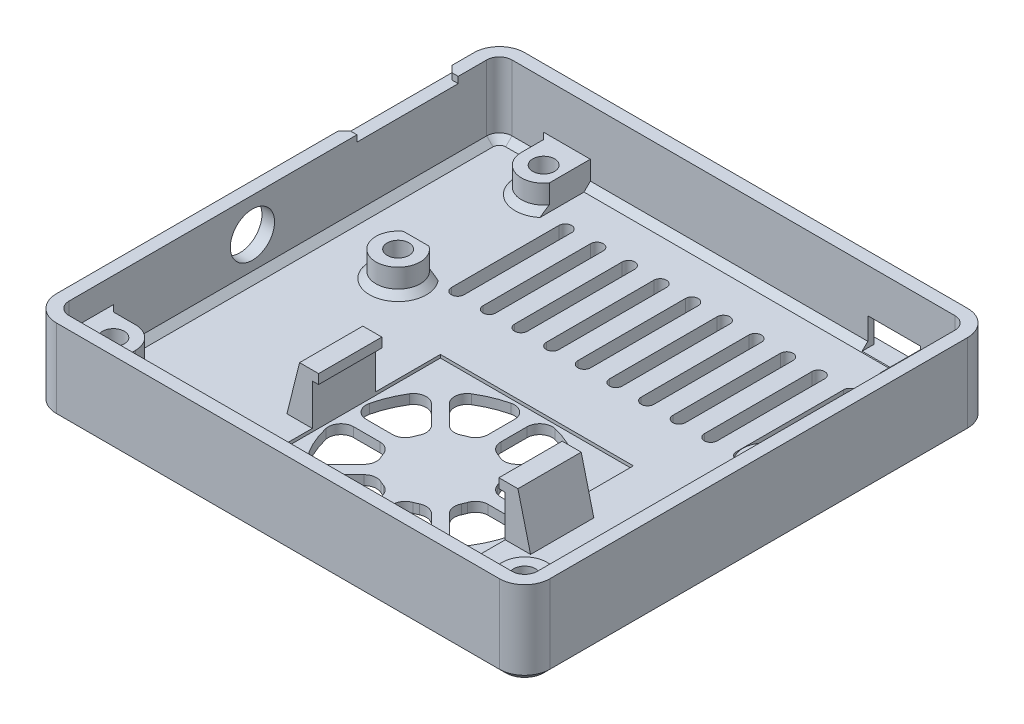
SolidWorks part; units mm, degrees
ref_plane "Front Plane" through (0, 0, 0) normal (0, 0, 1) x (1, 0, 0)
ref_plane "Top Plane" through (0, 0, 0) normal (0, 1, 0) x (1, 0, 0)
ref_plane "Right Plane" through (0, 0, 0) normal (1, 0, 0) x (0, 0, -1)
sketch "Sketch1" plane through (0, 0, 0) normal (0, 1, 0) x (1, 0, 0)
  line L0 (-65.617, -16.3721) -> (-0.617, -16.3721)
  line L1 (-62.117, 10.1279) -> (-4.117, 10.1279)
  line L2 (-62.117, 10.1279) -> (-62.117, -12.8721)
  line L3 (-65.617, 13.6279) -> (-0.617, 13.6279)
  line L4 (-65.617, 13.6279) -> (-65.617, -16.3721)
  line L5 (-62.117, -12.8721) -> (-4.117, -12.8721)
  line L6 (-0.617, 13.6279) -> (-0.617, -16.3721)
  line L7 (-4.117, 10.1279) -> (-4.117, -12.8721)
  line L8 (-24.217, 16.7282) -> (-24.217, 15.4455)
  line L9 (-11.617, 16.7282) -> (-11.617, 15.4455)
  dimension "D1" = 65
  dimension "D2" = 30
  dimension "D3" = 58
  dimension "D4" = 23
  dimension "D5" = 3.5
  dimension "D6" = 3.5
sketch "Sketch2" plane through (0, 0, 0) normal (0, 1, 0) x (1, 0, 0)
  line L6 (-73.617, 13.6279) -> (-73.617, -16.3721)
  line L7 (-73.617, 12.6279) -> (-73.617, -53.3721)
  line L10 (-71.617, -55.3721) -> (-1.617, -55.3721)
  line L11 (-75.617, 12.6279) -> (-75.617, -53.3721)
  line L12 (0.383, 14.6279) -> (0.383, -16.3721)
  line L13 (-65.617, 14.6279) -> (0.383, 14.6279)
  line L14 (0.383, 12.6279) -> (0.383, -53.3721)
  line L15 (-71.617, 14.6279) -> (-1.617, 14.6279)
  line L16 (-71.617, -57.3721) -> (-1.617, -57.3721)
  line L17 (2.383, 12.6279) -> (2.383, -53.3721)
  line L18 (-71.617, 16.6279) -> (-1.617, 16.6279)
  arc A0 (-71.617, -55.3721) -> (-73.617, -53.3721) centre (-71.617, -53.3721) cw
  arc A1 (-1.617, -55.3721) -> (0.383, -53.3721) centre (-1.617, -53.3721) ccw
  arc A2 (0.383, 12.6279) -> (-1.617, 14.6279) centre (-1.617, 12.6279) ccw
  arc A3 (-71.617, 14.6279) -> (-73.617, 12.6279) centre (-71.617, 12.6279) ccw
  arc A4 (-71.617, -57.3721) -> (-75.617, -53.3721) centre (-71.617, -53.3721) cw
  arc A5 (-1.617, -57.3721) -> (2.383, -53.3721) centre (-1.617, -53.3721) ccw
  arc A6 (2.383, 12.6279) -> (-1.617, 16.6279) centre (-1.617, 12.6279) ccw
  arc A7 (-71.617, 16.6279) -> (-75.617, 12.6279) centre (-71.617, 12.6279) ccw
  dimension "D4" = 2
  dimension "D3" = 70
  dimension "D1" = 8
  dimension "D2" = 1
  dimension "D5" = 2
extrude "Boss-Extrude1" add sketch "Sketch2" along normal blind 13.4
extrude "Boss-Extrude2" add sketch "Sketch2<3>" along normal blind 2 contours L15 A3 L7 A0 L10 A1 L14 A2 region at (-36.617, 0, 20.3721)
sketch "Sketch2<3>" plane through (0, 0, 0) normal (0, 1, 0) x (1, 0, 0) same geometry as "Sketch2"
sketch "Sketch4" plane through (0, 2, 0) normal (0, 1, 0) x (1, 0, 0)
  line L0 (-59.2343, 14.6279) -> (-59.2343, 8.1428)
  line L1 (-1.617, 14.6279) -> (-71.617, 14.6279) construction
  line L2 (-4.117, 6.6279) -> (0.383, 6.6279)
  line L3 (0.383, -53.3721) -> (0.383, 12.6279) construction
  line L4 (0.383, 6.6279) -> (0.383, 12.6279)
  line L5 (-7.0825, 14.6279) -> (-1.617, 14.6279)
  line L6 (-4.117, -9.3721) -> (0.383, -9.3721)
  line L7 (0.383, -9.3721) -> (0.383, -16.3721)
  line L8 (0.383, -16.3721) -> (-4.117, -16.3721)
  line L9 (-64.1397, -10.0158) -> (-60.0943, -10.0158)
  line L10 (-59.2343, 14.6279) -> (-65.617, 14.6279)
  line L11 (-65.617, 14.6279) -> (-65.617, 10.1279)
  line L12 (-7.0825, 14.6279) -> (-7.0825, 8.269)
  arc A0 (-7.0825, 8.269) -> (-4.117, 6.6279) centre (-4.117, 10.1279) ccw
  arc A1 (-4.117, -9.3721) -> (-4.117, -16.3721) centre (-4.117, -12.8721) ccw
  arc A2 (-64.1397, -10.0158) -> (-60.0943, -10.0158) centre (-62.117, -12.8721) ccw
  arc A3 (-65.617, 10.1279) -> (-59.2343, 8.1428) centre (-62.117, 10.1279) ccw
  arc A4 (0.383, 12.6279) -> (-1.617, 14.6279) centre (-1.617, 12.6279) ccw
  dimension "D1" = 2
extrude "Boss-Extrude3" add sketch "Sketch4" along normal offset from surface (4 mm away) 7.4 up to face at (-36.617, 13.4, 20.3721)
hole_wizard "CSK for #4 Flat Head Socket Cap Screw1" positions "Sketch6" profile "Sketch5" countersink size "#4" standard "ANSI Inch" end condition through all
sketch "Sketch6" plane through (0, 0, 0) normal (0, -1, 0) x (-1, 0, 0)
  point P0 (4.117, 10.1279)
  point P4 (62.117, 10.1279)
  point P8 (4.117, -12.8721)
  point P12 (62.117, -12.8721)
sketch "Sketch5" plane through (-4.117, 0, -10.1279) normal (1, 0, 0) x (0, 0, -1)
  line L0 (0, 0) -> (0, 13.4)
  line L1 (0, 13.4) -> (1.7272, 13.4)
  line L2 (1.7272, 13.4) -> (1.7272, 1.8805)
  line L3 (1.7272, 1.8805) -> (3.3619, 0)
  line L5 (3.3619, 0) -> (0, 0)
  line L6 (-1.7272, 1.8805) -> (-3.3619, 0) construction
  line L11 (0, -6.35) -> (0, 107.95) construction
  dimension "Thru Hole Dia." = 3.4544
  dimension "Thru Hole Depth" = 13.4
  dimension "Near C'Sink Dia." = 6.7237
  dimension "Near C'Sink Angle" = 82
sketch "Sketch7" plane through (0, 0, -16.6279) normal (0, 0, -1) x (-1, 0, 0)
  line L0 (11.2325, 6.5) -> (11.2325, 2.1) construction
  line L1 (7.0825, 6.5) -> (15.3825, 6.5)
  line L2 (7.0825, 6.5) -> (7.0825, 2.1)
  line L3 (7.0825, 2.1) -> (15.3825, 2.1)
  line L4 (15.3825, 6.5) -> (15.3825, 2.1)
  line L5 (1.617, 6) -> (7.0825, 6) construction
  line L7 (7.0825, 6) -> (7.0825, 2) construction
  dimension "D1" = 8.3
  dimension "D2" = 0.5
  dimension "D3" = 0
  dimension "D4" = 4.4
extrude "Cut-Extrude1" cut sketch "Sketch7" against normal up to next
sketch "Sketch9" plane through (0, 2, 0) normal (0, 1, 0) x (1, 0, 0)
  line L0 (0.383, -16.3721) -> (0.383, -53.3721) construction
  line L1 (-71.617, -55.3721) -> (-1.617, -55.3721) construction
  line L2 (-73.617, 12.6279) -> (-73.617, -53.3721) construction
  line L3 (-69.117, -47.3721) -> (-73.617, -47.3721)
  line L4 (-65.617, -50.8721) -> (-65.617, -55.3721)
  line L5 (-71.617, -55.3721) -> (-1.617, -55.3721) construction
  line L6 (-73.617, -47.3721) -> (-73.617, -53.3721)
  line L7 (-65.617, -55.3721) -> (-71.617, -55.3721)
  line L8 (-4.117, -47.3721) -> (0.383, -47.3721)
  line L9 (0.383, -47.3721) -> (0.383, -53.3721)
  line L10 (-7.617, -50.8721) -> (-7.617, -55.3721)
  line L11 (-7.617, -55.3721) -> (-1.617, -55.3721)
  arc A0 (-4.117, -47.3721) -> (-7.617, -50.8721) centre (-4.117, -50.8721) ccw
  arc A1 (-65.617, -50.8721) -> (-69.117, -47.3721) centre (-69.117, -50.8721) ccw
  arc A2 (-73.617, -53.3721) -> (-71.617, -55.3721) centre (-71.617, -53.3721) ccw
  arc A3 (-1.617, -55.3721) -> (0.383, -53.3721) centre (-1.617, -53.3721) ccw
  dimension "D1" = 4.5
  dimension "D2" = 4.5
  dimension "D3" = 4.5
  dimension "D4" = 4.5
  dimension "D5" = 2
  dimension "D6" = 2
extrude "Boss-Extrude4" add sketch "Sketch9" along normal offset from surface (7.4 mm away) 4 up to face at (-36.617, 13.4, 20.3721)
hole_wizard "CSK for #4 Flat Head Socket Cap Screw2" positions "Sketch11" profile "Sketch10" countersink size "#4" standard "ANSI Inch" end condition through all
sketch "Sketch11" plane through (0, 0, 0) normal (0, -1, 0) x (-1, 0, 0)
  point P0 (4.117, -50.8721)
  point P4 (69.117, -50.8721)
sketch "Sketch10" plane through (-4.117, 0, 50.8721) normal (1, 0, 0) x (0, 0, -1)
  line L0 (0, 0) -> (0, 13.4)
  line L1 (0, 13.4) -> (1.7272, 13.4)
  line L2 (1.7272, 13.4) -> (1.7272, 1.8805)
  line L3 (1.7272, 1.8805) -> (3.3619, 0)
  line L5 (3.3619, 0) -> (0, 0)
  line L6 (-1.7272, 1.8805) -> (-3.3619, 0) construction
  line L11 (0, -6.35) -> (0, 107.95) construction
  dimension "Thru Hole Dia." = 3.4544
  dimension "Thru Hole Depth" = 13.4
  dimension "Near C'Sink Dia." = 6.7237
  dimension "Near C'Sink Angle" = 82
chamfer "Chamfer1" distance 1 angle 45 8 edges at (-65.617, 4, -14.6279) (-65.617, 5.7, 55.3721) (-73.617, 5.7, 47.3721) (0.383, 4, 9.3721) (0.383, 4, -6.6279) (0.383, 4, 16.3721) (0.383, 5.7, 47.3721) (-7.617, 5.7, 55.3721)
chamfer "Chamfer2" distance 1 angle 45 21 edges at (-62.117, 2, 16.3721) (-65.617, 2, -11.8779) (-63.1564, 2, -6.7858) (-2.367, 2, -6.6279) (-5.8117, 2, -7.0655) (0.383, 2, 1.3721) (-2.367, 2, 9.3721) (-2.367, 2, 16.3721) (0.383, 2, 31.8721) (-2.367, 2, 47.3721) (-7.617, 2, 52.6221) (-6.5919, 2, 48.3973) (-36.617, 2, 55.3721) (-65.617, 2, 52.6221) (-70.867, 2, 47.3721) (-66.6421, 2, 48.3973) (-69.117, 2, -14.6279) (-73.0312, 2, -14.0421) (-73.617, 2, 16.8721) (-7.617, 2, 12.8721) (-33.1584, 2, -14.6279)
chamfer "Chamfer3" distance 1 angle 45 8 edges at (2.383, 0, 20.3721) (1.2114, 0, -15.4563) (1.2114, 0, 56.2006) (-36.617, 0, -16.6279) (-36.617, 0, 57.3721) (-74.4454, 0, -15.4563) (-74.4454, 0, 56.2006) (-75.617, 0, 20.3721)
chamfer "Chamfer4" distance 1 angle 45 2 edges at (-15.3825, 4.3, -16.6279) (-7.0825, 4.3, -16.6279)
sketch "Sketch12" plane through (0, 0, 0) normal (0, -1, 0) x (1, 0, 0)
  line L0 (-55.6605, 9.9113) -> (-55.6605, -7.0887) construction
  line L1 (-54.6605, 9.9113) -> (-54.6605, -7.0887)
  line L2 (-56.6605, 9.9113) -> (-56.6605, -7.0887)
  line L3 (-50.6605, 9.9113) -> (-50.6605, -7.0887) construction
  line L4 (-49.6605, 9.9113) -> (-49.6605, -7.0887)
  line L5 (-51.6605, 9.9113) -> (-51.6605, -7.0887)
  line L6 (-45.6605, 9.9113) -> (-45.6605, -7.0887) construction
  line L7 (-44.6605, 9.9113) -> (-44.6605, -7.0887)
  line L8 (-46.6605, 9.9113) -> (-46.6605, -7.0887)
  line L9 (-40.6605, 9.9113) -> (-40.6605, -7.0887) construction
  line L10 (-39.6605, 9.9113) -> (-39.6605, -7.0887)
  line L11 (-41.6605, 9.9113) -> (-41.6605, -7.0887)
  line L12 (-35.6605, 9.9113) -> (-35.6605, -7.0887) construction
  line L13 (-34.6605, 9.9113) -> (-34.6605, -7.0887)
  line L14 (-36.6605, 9.9113) -> (-36.6605, -7.0887)
  line L15 (-30.6605, 9.9113) -> (-30.6605, -7.0887) construction
  line L16 (-29.6605, 9.9113) -> (-29.6605, -7.0887)
  line L17 (-31.6605, 9.9113) -> (-31.6605, -7.0887)
  line L18 (-25.6605, 9.9113) -> (-25.6605, -7.0887) construction
  line L19 (-24.6605, 9.9113) -> (-24.6605, -7.0887)
  line L20 (-26.6605, 9.9113) -> (-26.6605, -7.0887)
  line L21 (-20.6605, 9.9113) -> (-20.6605, -7.0887) construction
  line L22 (-19.6605, 9.9113) -> (-19.6605, -7.0887)
  line L23 (-21.6605, 9.9113) -> (-21.6605, -7.0887)
  line L24 (-15.6605, 9.9113) -> (-15.6605, -7.0887) construction
  line L25 (-14.6605, 9.9113) -> (-14.6605, -7.0887)
  line L26 (-16.6605, 9.9113) -> (-16.6605, -7.0887)
  line L27 (-10.6605, 9.9113) -> (-10.6605, -7.0887) construction
  line L28 (-9.6605, 9.9113) -> (-9.6605, -7.0887)
  line L29 (-11.6605, 9.9113) -> (-11.6605, -7.0887)
  arc A0 (-54.6605, 9.9113) -> (-56.6605, 9.9113) centre (-55.6605, 9.9113) ccw
  arc A1 (-56.6605, -7.0887) -> (-54.6605, -7.0887) centre (-55.6605, -7.0887) ccw
  arc A2 (-49.6605, 9.9113) -> (-51.6605, 9.9113) centre (-50.6605, 9.9113) ccw
  arc A3 (-51.6605, -7.0887) -> (-49.6605, -7.0887) centre (-50.6605, -7.0887) ccw
  arc A4 (-44.6605, 9.9113) -> (-46.6605, 9.9113) centre (-45.6605, 9.9113) ccw
  arc A5 (-46.6605, -7.0887) -> (-44.6605, -7.0887) centre (-45.6605, -7.0887) ccw
  arc A6 (-39.6605, 9.9113) -> (-41.6605, 9.9113) centre (-40.6605, 9.9113) ccw
  arc A7 (-41.6605, -7.0887) -> (-39.6605, -7.0887) centre (-40.6605, -7.0887) ccw
  arc A8 (-34.6605, 9.9113) -> (-36.6605, 9.9113) centre (-35.6605, 9.9113) ccw
  arc A9 (-36.6605, -7.0887) -> (-34.6605, -7.0887) centre (-35.6605, -7.0887) ccw
  arc A10 (-29.6605, 9.9113) -> (-31.6605, 9.9113) centre (-30.6605, 9.9113) ccw
  arc A11 (-31.6605, -7.0887) -> (-29.6605, -7.0887) centre (-30.6605, -7.0887) ccw
  arc A12 (-24.6605, 9.9113) -> (-26.6605, 9.9113) centre (-25.6605, 9.9113) ccw
  arc A13 (-26.6605, -7.0887) -> (-24.6605, -7.0887) centre (-25.6605, -7.0887) ccw
  arc A14 (-19.6605, 9.9113) -> (-21.6605, 9.9113) centre (-20.6605, 9.9113) ccw
  arc A15 (-21.6605, -7.0887) -> (-19.6605, -7.0887) centre (-20.6605, -7.0887) ccw
  arc A16 (-14.6605, 9.9113) -> (-16.6605, 9.9113) centre (-15.6605, 9.9113) ccw
  arc A17 (-16.6605, -7.0887) -> (-14.6605, -7.0887) centre (-15.6605, -7.0887) ccw
  arc A18 (-9.6605, 9.9113) -> (-11.6605, 9.9113) centre (-10.6605, 9.9113) ccw
  arc A19 (-11.6605, -7.0887) -> (-9.6605, -7.0887) centre (-10.6605, -7.0887) ccw
  point P2 (-55.6605, 1.4113)
  point P10 (-50.6605, 1.4113)
  point P17 (-45.6605, 1.4113)
  point P24 (-40.6605, 1.4113)
  point P31 (-35.6605, 1.4113)
  point P38 (-30.6605, 1.4113)
  point P45 (-25.6605, 1.4113)
  point P52 (-20.6605, 1.4113)
  point P59 (-15.6605, 1.4113)
  point P66 (-10.6605, 1.4113)
  dimension "D1" = 2
  dimension "D2" = 17
  dimension "D3" = 10
extrude "Cut-Extrude2" cut sketch "Sketch12" against normal up to next
sketch "Sketch13" plane through (0, 2, 0) normal (0, 1, 0) x (1, 0, 0)
  line L1 (-17.867, -50.4402) -> (-48.367, -50.4402)
  line L2 (-17.867, -50.4402) -> (-17.867, -19.9402)
  line L3 (-17.867, -19.9402) -> (-48.367, -19.9402)
  line L4 (-48.367, -50.4402) -> (-48.367, -19.9402)
  dimension "D1" = 30.5
  dimension "D2" = 30.5
extrude "Cut-Extrude3" cut sketch "Sketch13" against normal blind 0.5
sketch "Sketch14" plane through (0, 2, 0) normal (0, 1, 0) x (1, 0, 0)
  line L0 (-48.367, -40.1902) -> (-50.367, -40.1902)
  line L1 (-15.867, -40.1902) -> (-17.867, -40.1902)
  line L2 (-15.867, -40.1902) -> (-15.867, -30.1902)
  line L3 (-15.867, -30.1902) -> (-17.867, -30.1902)
  line L4 (-17.867, -40.1902) -> (-17.867, -30.1902)
  line L5 (-48.367, -30.1902) -> (-50.367, -30.1902)
  line L6 (-50.367, -40.1902) -> (-50.367, -30.1902)
  line L7 (-48.367, -40.1902) -> (-48.367, -30.1902)
  dimension "D1" = 10
  dimension "D2" = 2
  dimension "D3" = 10
extrude "Boss-Extrude5" add sketch "Sketch14" along normal blind 8
sketch "Sketch15" plane through (-17.867, 0, 0) normal (-1, 0, 0) x (0, 0, 1)
  line L0 (30.1902, 10) -> (30.1902, 2) construction
  line L1 (40.1902, 10) -> (30.1902, 10)
  line L2 (40.1902, 10) -> (40.1902, 8.5)
  line L3 (40.1902, 8.5) -> (30.1902, 8.5)
  line L4 (30.1902, 10) -> (30.1902, 8.5)
  line L5 (30.1902, 10) -> (40.1902, 10) construction
  dimension "D1" = 1.5
extrude "Boss-Extrude6" add sketch "Sketch15" along normal blind 1
sketch "Sketch16" plane through (-48.367, 0, 0) normal (1, 0, 0) x (0, 0, -1)
  line L0 (-30.1902, 10) -> (-30.1902, 2) construction
  line L1 (-40.1902, 10) -> (-30.1902, 10)
  line L2 (-40.1902, 10) -> (-40.1902, 8.5)
  line L3 (-40.1902, 8.5) -> (-30.1902, 8.5)
  line L4 (-30.1902, 10) -> (-30.1902, 8.5)
  dimension "D1" = 1.5
extrude "Boss-Extrude7" add sketch "Sketch16" along normal blind 1
chamfer "Chamfer5" distance 2 angle 76 2 edges at (-50.367, 2, 35.1902) (-15.867, 2, 35.1902) first distance on face at (-10.6605, 2, 1.4113)
sketch "Sketch17" plane through (0, 1.5, 0) normal (0, 1, 0) x (1, 0, 0)
  line L0 (-41.3961, -25.4969) -> (-38.4532, -28.4398)
  line L1 (-34.117, -22.4818) -> (-34.117, -26.6437)
  line L2 (-32.117, -22.4818) -> (-32.117, -26.6437)
  line L3 (-24.8379, -25.4969) -> (-27.7808, -28.4398)
  line L4 (-23.4236, -26.9111) -> (-26.3666, -29.854)
  line L5 (-20.4085, -34.1902) -> (-24.5705, -34.1902)
  line L6 (-20.4085, -36.1902) -> (-24.5705, -36.1902)
  line L7 (-23.4236, -43.4693) -> (-26.3666, -40.5264)
  line L8 (-24.8379, -44.8835) -> (-27.7808, -41.9406)
  line L9 (-32.117, -47.8987) -> (-32.117, -43.7367)
  line L10 (-34.117, -47.8987) -> (-34.117, -43.7367)
  line L11 (-41.3961, -44.8835) -> (-38.4532, -41.9406)
  line L12 (-42.8103, -43.4693) -> (-39.8674, -40.5264)
  line L13 (-45.8254, -36.1902) -> (-41.6635, -36.1902)
  line L14 (-45.8254, -34.1902) -> (-41.6635, -34.1902)
  line L15 (-42.8103, -26.9111) -> (-39.8674, -29.854)
  arc A0 (-45.9258, -27.2738) -> (-47.7719, -31.7307) centre (-33.117, -35.1902) ccw
  arc A1 (-39.4788, -32.1342) -> (-39.7764, -32.8526) centre (-33.117, -35.1902) ccw
  arc A2 (-39.4788, -32.1342) -> (-39.8674, -29.854) centre (-41.2816, -31.2682) ccw
  arc A3 (-41.6635, -34.1902) -> (-39.7764, -32.8526) centre (-41.6635, -32.1902) ccw
  arc A4 (-45.8254, -34.1902) -> (-47.7719, -31.7307) centre (-45.8254, -32.1902) cw
  arc A5 (-42.8103, -26.9111) -> (-45.9258, -27.2738) centre (-44.2245, -28.3253) ccw
  arc A6 (-36.5765, -20.5353) -> (-41.0334, -22.3814) centre (-33.117, -35.1902) ccw
  arc A7 (-35.4546, -28.5308) -> (-36.173, -28.8284) centre (-33.117, -35.1902) ccw
  arc A8 (-35.4546, -28.5308) -> (-34.117, -26.6437) centre (-36.117, -26.6437) ccw
  arc A9 (-38.4532, -28.4398) -> (-36.173, -28.8284) centre (-37.039, -27.0256) ccw
  arc A10 (-41.3961, -25.4969) -> (-41.0334, -22.3814) centre (-39.9819, -24.0827) cw
  arc A11 (-34.117, -22.4818) -> (-36.5765, -20.5353) centre (-36.117, -22.4818) ccw
  arc A12 (-25.2006, -22.3814) -> (-29.6575, -20.5353) centre (-33.117, -35.1902) ccw
  arc A13 (-30.061, -28.8284) -> (-30.7794, -28.5308) centre (-33.117, -35.1902) ccw
  arc A14 (-30.061, -28.8284) -> (-27.7808, -28.4398) centre (-29.195, -27.0256) ccw
  arc A15 (-32.117, -26.6437) -> (-30.7794, -28.5308) centre (-30.117, -26.6437) ccw
  arc A16 (-32.117, -22.4818) -> (-29.6575, -20.5353) centre (-30.117, -22.4818) cw
  arc A17 (-24.8379, -25.4969) -> (-25.2006, -22.3814) centre (-26.2521, -24.0827) ccw
  arc A18 (-18.462, -31.7307) -> (-20.3081, -27.2738) centre (-33.117, -35.1902) ccw
  arc A19 (-26.4576, -32.8526) -> (-26.7552, -32.1342) centre (-33.117, -35.1902) ccw
  arc A20 (-26.4576, -32.8526) -> (-24.5705, -34.1902) centre (-24.5705, -32.1902) ccw
  arc A21 (-26.3666, -29.854) -> (-26.7552, -32.1342) centre (-24.9524, -31.2682) ccw
  arc A22 (-23.4236, -26.9111) -> (-20.3081, -27.2738) centre (-22.0094, -28.3253) cw
  arc A23 (-20.4085, -34.1902) -> (-18.462, -31.7307) centre (-20.4085, -32.1902) ccw
  arc A24 (-20.3081, -43.1066) -> (-18.462, -38.6497) centre (-33.117, -35.1902) ccw
  arc A25 (-26.7552, -38.2462) -> (-26.4576, -37.5278) centre (-33.117, -35.1902) ccw
  arc A26 (-26.7552, -38.2462) -> (-26.3666, -40.5264) centre (-24.9524, -39.1122) ccw
  arc A27 (-24.5705, -36.1902) -> (-26.4576, -37.5278) centre (-24.5705, -38.1902) ccw
  arc A28 (-20.4085, -36.1902) -> (-18.462, -38.6497) centre (-20.4085, -38.1902) cw
  arc A29 (-23.4236, -43.4693) -> (-20.3081, -43.1066) centre (-22.0094, -42.0551) ccw
  arc A30 (-29.6575, -49.8452) -> (-25.2006, -47.9991) centre (-33.117, -35.1902) ccw
  arc A31 (-30.7794, -41.8496) -> (-30.061, -41.552) centre (-33.117, -35.1902) ccw
  arc A32 (-30.7794, -41.8496) -> (-32.117, -43.7367) centre (-30.117, -43.7367) ccw
  arc A33 (-27.7808, -41.9406) -> (-30.061, -41.552) centre (-29.195, -43.3548) ccw
  arc A34 (-24.8379, -44.8835) -> (-25.2006, -47.9991) centre (-26.2521, -46.2978) cw
  arc A35 (-32.117, -47.8987) -> (-29.6575, -49.8452) centre (-30.117, -47.8987) ccw
  arc A36 (-41.0334, -47.9991) -> (-36.5765, -49.8452) centre (-33.117, -35.1902) ccw
  arc A37 (-36.173, -41.552) -> (-35.4546, -41.8496) centre (-33.117, -35.1902) ccw
  arc A38 (-36.173, -41.552) -> (-38.4532, -41.9406) centre (-37.039, -43.3548) ccw
  arc A39 (-34.117, -43.7367) -> (-35.4546, -41.8496) centre (-36.117, -43.7367) ccw
  arc A40 (-34.117, -47.8987) -> (-36.5765, -49.8452) centre (-36.117, -47.8987) cw
  arc A41 (-41.3961, -44.8835) -> (-41.0334, -47.9991) centre (-39.9819, -46.2978) ccw
  arc A42 (-47.7719, -38.6497) -> (-45.9258, -43.1066) centre (-33.117, -35.1902) ccw
  arc A43 (-39.7764, -37.5278) -> (-39.4788, -38.2462) centre (-33.117, -35.1902) ccw
  arc A44 (-39.7764, -37.5278) -> (-41.6635, -36.1902) centre (-41.6635, -38.1902) ccw
  arc A45 (-39.8674, -40.5264) -> (-39.4788, -38.2462) centre (-41.2816, -39.1122) ccw
  arc A46 (-42.8103, -43.4693) -> (-45.9258, -43.1066) centre (-44.2245, -42.0551) cw
  arc A47 (-45.8254, -36.1902) -> (-47.7719, -38.6497) centre (-45.8254, -38.1902) ccw
  point P41 (-33.117, -35.1902)
  point P98 (-33.117, -35.1902)
  dimension "D1" = 2
extrude "Cut-Extrude4" cut sketch "Sketch17" against normal through all
sketch "Sketch18" plane through (-73.617, 0, 0) normal (1, 0, 0) x (0, 0, -1)
  circle A0 centre (-24.3941, 7.9996) radius 3.5
  dimension "D1" = 7
extrude "Cut-Extrude5" cut sketch "Sketch18" against normal through all
sketch "Sketch19" plane through (-75.617, 0, 0) normal (-1, 0, 0) x (0, 0, 1)
  line L0 (-12.6279, 13.4) -> (53.3721, 13.4) construction
  line L1 (-8.1279, 13.4) -> (7.8721, 13.4)
  line L2 (-8.1279, 13.4) -> (-8.1279, 12.4)
  line L3 (-8.1279, 12.4) -> (7.8721, 12.4)
  line L4 (7.8721, 13.4) -> (7.8721, 12.4)
  line L5 (-12.6279, 13.4) -> (-12.6279, 1) construction
  point P6 (-8.1279, 12.9)
  dimension "D1" = 16
  dimension "D2" = 4.5
  dimension "D3" = 1
extrude "Cut-Extrude6" cut sketch "Sketch19" against normal up to next
chamfer "Chamfer6" distance 1 angle 45 2 edges at (-75.617, 12.9, 7.8721) (-75.617, 12.9, -8.1279)
